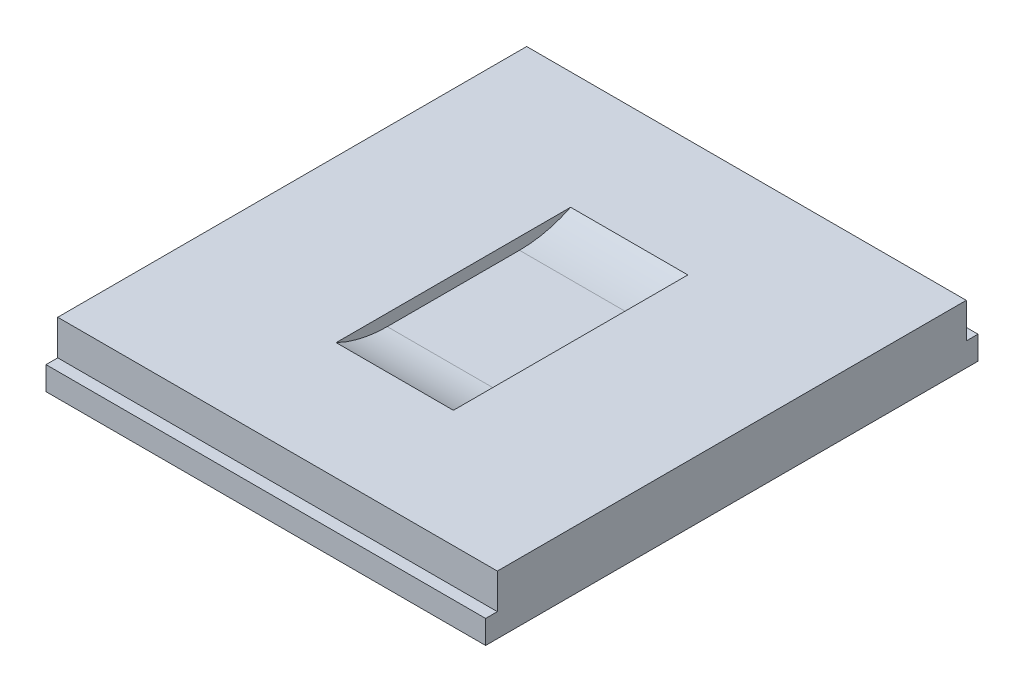
SolidWorks part; units mm, degrees
ref_plane "Front Plane" through (0, 0, 0) normal (0, 0, 1) x (1, 0, 0)
ref_plane "Top Plane" through (0, 0, 0) normal (0, 1, 0) x (1, 0, 0)
ref_plane "Right Plane" through (0, 0, 0) normal (1, 0, 0) x (0, 0, -1)
sketch "Sketch1" plane through (0, 0, 0) normal (0, 1, 0) x (1, 0, 0)
  line L1 (-18.75, -21) -> (18.75, -21)
  line L2 (-18.75, -21) -> (-18.75, 21)
  line L3 (-18.75, 21) -> (18.75, 21)
  line L4 (18.75, -21) -> (18.75, 21)
  line L5 (-18.75, -21) -> (18.75, 21) construction
  line L6 (-18.75, 21) -> (18.75, -21) construction
  point P0 (0, 0)
extrude "Boss-Extrude1" add sketch "Sketch1" along normal blind 5 contours L2 L3 L4 L1
sketch "Sketch2" plane through (0, 5, 0) normal (0, 1, 0) x (1, 0, 0)
  line L0 (18.75, -21) -> (18.75, 21) construction
  line L1 (-18.75, -21) -> (18.75, -21)
  line L2 (-18.75, -21) -> (-18.75, -20)
  line L3 (-18.75, -20) -> (18.75, -20)
  line L4 (18.75, -21) -> (18.75, -20)
extrude "Cut-Extrude1" cut sketch "Sketch2" against normal blind 3
sketch "Sketch3" plane through (0, 5, 0) normal (0, 1, 0) x (1, 0, 0)
  line L0 (18.75, -20) -> (18.75, 21) construction
  line L1 (-18.75, 21) -> (18.75, 21)
  line L2 (-18.75, 21) -> (-18.75, 20)
  line L3 (-18.75, 20) -> (18.75, 20)
  line L4 (18.75, 21) -> (18.75, 20)
extrude "Cut-Extrude2" cut sketch "Sketch3" against normal blind 3
sketch "Sketch4" plane through (0, 5, 0) normal (0, 1, 0) x (1, 0, 0)
  line L1 (-5, -10) -> (5, -10)
  line L2 (-5, -10) -> (-5, 10)
  line L3 (-5, 10) -> (5, 10)
  line L4 (5, -10) -> (5, 10)
  line L5 (-5, -10) -> (5, 10) construction
  line L6 (-5, 10) -> (5, -10) construction
  point P0 (0, 0)
extrude "Cut-Extrude3" cut sketch "Sketch4" against normal blind 1
fillet "Fillet1" radius 10 1 edges at (0, 4, -10)
fillet "Fillet2" radius 10 1 edges at (0, 4, 10)
